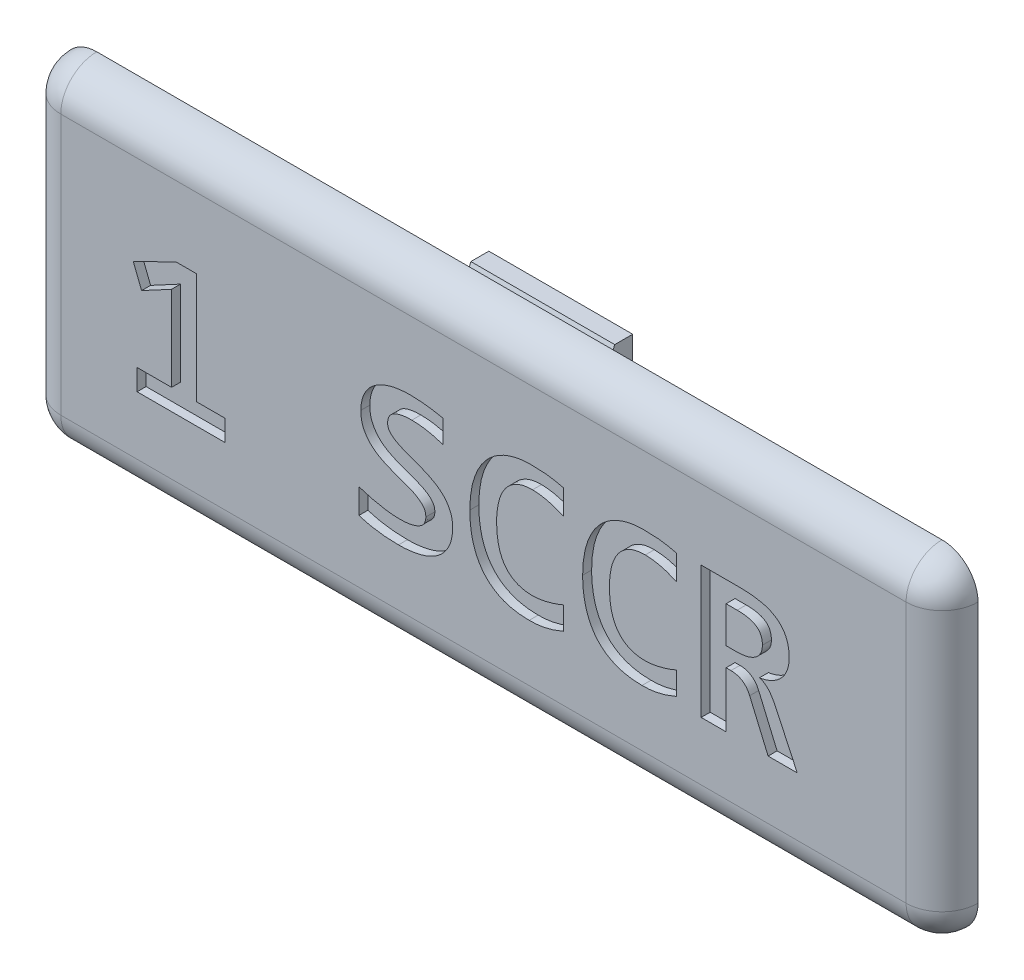
SolidWorks part; units mm, degrees
ref_plane "Front Plane" through (0, 0, 0) normal (0, 0, 1) x (1, 0, 0)
ref_plane "Top Plane" through (0, 0, 0) normal (0, 1, 0) x (1, 0, 0)
ref_plane "Right Plane" through (0, 0, 0) normal (1, 0, 0) x (0, 0, -1)
sketch "Sketch1" plane through (0, 0, 0) normal (0, 0, 1) x (1, 0, 0)
  line L13 (25.5, -7.25) -> (25.5, 7.25) construction
  line L14 (-23.5, -9.25) -> (-5, -9.25) construction
  line L15 (-25.5, 7.25) -> (-25.5, -7.25) construction
  line L16 (13, 9.25) -> (-23.5, 9.25) construction
  line L17 (25.5, -7.25) -> (25.5, 7.25)
  line L18 (-23.5, -9.25) -> (23.5, -9.25)
  line L19 (-25.5, 7.25) -> (-25.5, -7.25)
  line L20 (23.5, 9.25) -> (-23.5, 9.25)
  line L28 (23.75, -7.75) -> (23.75, 7.75)
  line L29 (-23.75, -7.5) -> (11.5, -7.5)
  line L30 (-23.75, 7.5) -> (-23.75, -7.5)
  line L31 (13, 7.5) -> (-23.75, 7.5)
  line L32 (-23.75, -7.5) -> (23.75, -7.5) construction
  line L33 (-23.75, 7.5) -> (-23.75, -7.5) construction
  line L34 (23.75, 7.5) -> (-23.75, 7.5) construction
  line L35 (23.75, -7.75) -> (23.75, 7.75) construction
  arc A0 (25.5, 7.25) -> (23.5, 9.25) centre (23.5, 7.25) ccw construction
  arc A1 (23.5, -9.25) -> (25.5, -7.25) centre (23.5, -7.25) ccw construction
  arc A2 (-25.5, -7.25) -> (-23.5, -9.25) centre (-23.5, -7.25) ccw construction
  arc A3 (-23.5, 9.25) -> (-25.5, 7.25) centre (-23.5, 7.25) ccw construction
  arc A4 (25.5, 7.25) -> (23.5, 9.25) centre (23.5, 7.25) ccw
  arc A5 (23.5, -9.25) -> (25.5, -7.25) centre (23.5, -7.25) ccw
  arc A6 (-25.5, -7.25) -> (-23.5, -9.25) centre (-23.5, -7.25) ccw
  arc A7 (-23.5, 9.25) -> (-25.5, 7.25) centre (-23.5, 7.25) ccw
  dimension "D1" = 0.25
  dimension "D2" = 0.25
extrude "Boss-Extrude1" add sketch "Sketch1" along normal blind 2
sketch "Sketch3" plane through (0, 0, 0) normal (0, 0, -1) x (-1, 0, 0)
  line L0 (-23.75, -7.75) -> (-23.75, 7.75) construction
  line L1 (-23.75, 7.5) -> (23.75, 7.5) construction
  line L2 (23.75, 7.5) -> (23.75, -7.5) construction
  line L3 (23.75, -7.5) -> (-23.75, -7.5) construction
  line L4 (-23.75, -7.5) -> (-23.75, 7.5)
  line L5 (-23.75, 7.5) -> (23.75, 7.5)
  line L6 (23.75, 7.5) -> (23.75, -7.5)
  line L7 (23.75, -7.5) -> (-23.75, -7.5)
extrude "Boss-Extrude2" add sketch "Sketch3" along normal blind 1
sketch "Sketch4" plane through (0, 0, -1) normal (0, 0, -1) x (-1, 0, 0)
  line L0 (-23.75, -7.5) -> (23.75, -7.5) construction
  line L1 (-8.75, -7.5) -> (-18.25, -7.5)
  line L2 (-8.75, -7.5) -> (-8.75, -2.5)
  line L3 (-8.75, -2.5) -> (-18.25, -2.5)
  line L4 (-18.25, -7.5) -> (-18.25, -2.5)
  line L5 (-11.5, -7.75) -> (-15.5, -7.75) construction
  point P4 (-13.5, -2.5)
  point P9 (-13.5, -7.75)
  dimension "D1" = 5
  dimension "D3" = 9.5
extrude "Cut-Extrude1" cut sketch "Sketch4" against normal blind 1
sketch "Sketch5" plane through (0, 0, -1) normal (0, 0, -1) x (-1, 0, 0)
  line L1 (-13, 7.75) -> (-21, 7.75)
  line L2 (-13, 7.75) -> (-13, -0.75)
  line L3 (-13, -0.75) -> (-21, -0.75)
  line L4 (-21, 7.75) -> (-21, -0.75)
  line L5 (-24, 7.75) -> (24, 7.75) construction
  dimension "D1" = 8
  dimension "D2" = 8.5
extrude "Cut-Extrude2" cut sketch "Sketch5" against normal blind 1
sketch "Sketch6" plane through (0, 0, 0) normal (0, 0, -1) x (-1, 0, 0)
  line L1 (-11.5, -9.25) -> (-15.5, -9.25)
  line L2 (-11.5, -9.25) -> (-11.5, -7.5)
  line L3 (-11.5, -7.5) -> (-15.5, -7.5)
  line L4 (-15.5, -9.25) -> (-15.5, -7.5)
  line L6 (23.75, -7.5) -> (-23.75, -7.5) construction
  line L8 (-11.5, -9.25) -> (-15.5, -9.25) construction
  line L9 (23.5, -9.25) -> (-23.5, -9.25) construction
  point P8 (-13.5, -7.5)
  point P11 (-13.5, -9.25)
  dimension "D1" = 4
extrude "Boss-Extrude3" add sketch "Sketch6" along normal blind 1.75
sketch "Sketch8" plane through (0, 0, 0) normal (1, 0, 0) x (0, 0, -1)
  line L1 (1, -7.5) -> (1, 7.5) construction
  line L2 (2.3, 6.05) -> (2.3, 8.25)
  line L3 (1, 5.25) -> (1, 7.5)
  line L4 (1, 7.5) -> (1.3, 8.25)
  line L5 (1.3, 8.25) -> (2.3, 8.25)
  line L6 (2.3, 6.05) -> (1, 5.25)
  dimension "D1" = 0.3
  dimension "D2" = 1
  dimension "D3" = 3
  dimension "D4" = 0.75
  dimension "D5" = 0.8
extrude "Boss-Extrude4" add sketch "Sketch8" against normal blind 4 and the other way blind 4
mirror "Mirror1" about plane through (0, 0, 0) normal (0, 1, 0) of "Boss-Extrude4"
fillet "Fillet1" radius 2 8 edges at (-24.9142, 8.6642, 2) (0, 9.25, 2) (24.9142, 8.6642, 2) (25.5, 0, 2) (24.9142, -8.6642, 2) (0, -9.25, 2) (-24.9142, -8.6642, 2) (-25.5, 0, 2)
sketch "Sketch9" plane through (0, 0, 2) normal (0, 0, 1) x (1, 0, 0)
  line L0 (-20, -4) -> (20, -4) construction
  line L1 (-23.75, -7.5) -> (23.75, -7.5) construction
  text T0 "<b>1 SCCR</b>" font "Consolas" height in points 28
  point P2 (0, -4)
  dimension "D1" = 40
  dimension "D2" = 3.5
extrude "Cut-Extrude3" cut sketch "Sketch9" against normal blind 0.5
